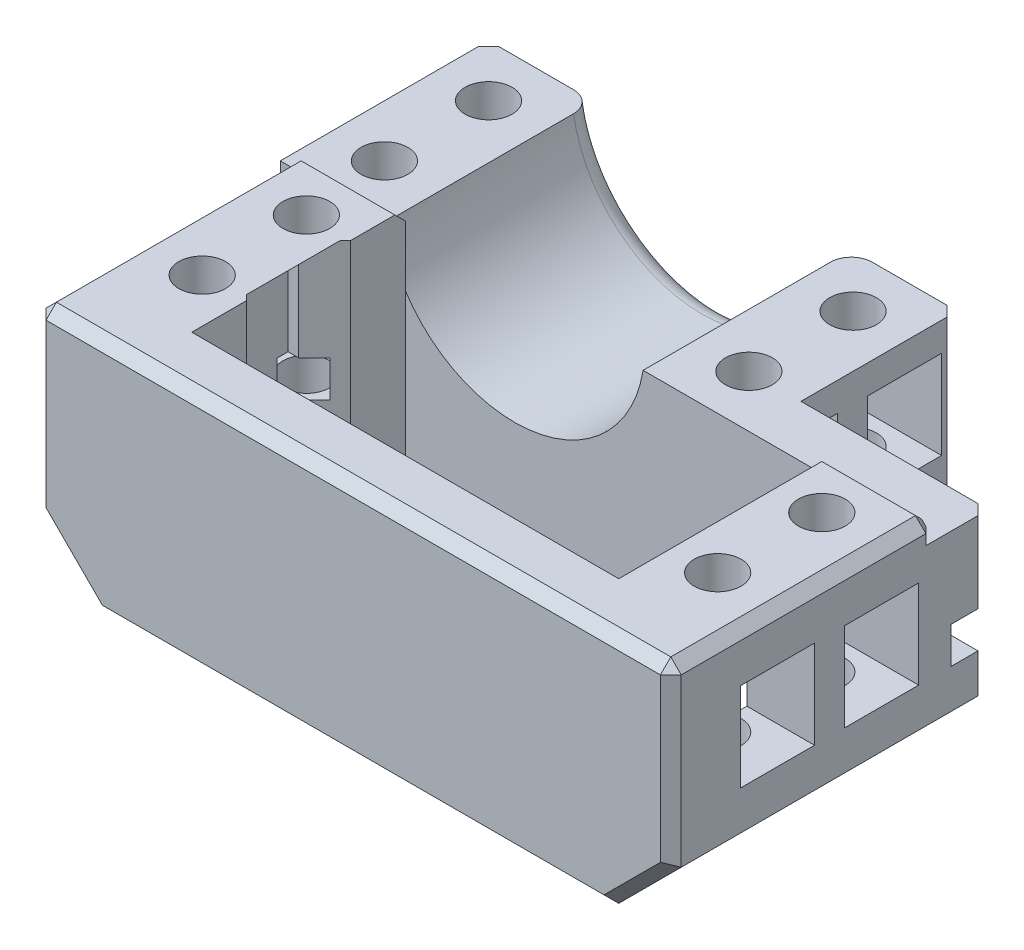
SolidWorks part; units mm, degrees
ref_plane "Front Plane" through (0, 0, 0) normal (0, 0, 1) x (1, 0, 0)
ref_plane "Top Plane" through (0, 0, 0) normal (0, 1, 0) x (1, 0, 0)
ref_plane "Right Plane" through (0, 0, 0) normal (1, 0, 0) x (0, 0, -1)
sketch "Sketch1" plane through (0, 0, 0) normal (0, 1, 0) x (1, 0, 0)
  line L0 (0, -10.25) -> (0, 10.25) construction
  line L1 (-20.5, 0) -> (20.5, 0) construction
  line L2 (-20.5, 10.25) -> (20.5, 10.25)
  line L3 (20.5, 10.25) -> (20.5, -10.25)
  line L4 (20.5, -10.25) -> (-20.5, -10.25)
  line L5 (-20.5, -10.25) -> (-20.5, 10.25)
  line L6 (0, -10.25) -> (0, -15.25) construction
  line L7 (0, -15.25) -> (-30.5, -15.25)
  line L8 (0, -15.25) -> (30.5, -15.25)
  line L9 (-30.5, -15.25) -> (-30.5, 30.25)
  line L10 (-30.5, 30.25) -> (30.5, 30.25)
  line L11 (30.5, 30.25) -> (30.5, -15.25)
  point P4 (0, 0)
  point P8 (0, 0)
  point P11 (0, 10.25)
  dimension "D1" = 41
  dimension "D2" = 20.5
  dimension "D3" = 5
  dimension "D4" = 30.5
  dimension "D5" = 30.5
  dimension "D6" = 45.5
extrude "Boss-Extrude1" add sketch "Sketch1" along normal blind 23
ref_plane "Plane1" through (0, 0, -30.25) normal (0, 0, -1) x (-1, 0, 0)
sketch "Sketch2" plane through (0, 0, -30.25) normal (0, 0, -1) x (-1, 0, 0)
  line L0 (0, 0) -> (0, 23) construction
  line L1 (-30.5, 23) -> (30.5, 23) construction
  line L2 (0, 23) -> (10, 23) construction
  circle A0 centre (10, 23) radius 12.5
  dimension "D2" = 25
  dimension "D1" = 10
extrude "Cut-Extrude1" cut sketch "Sketch2" against normal blind 20
ref_plane "Plane2" through (-30.5, 0, 0) normal (-1, 0, 0) x (0, 0, 1)
sketch "Sketch3" plane through (-30.5, 0, 0) normal (-1, 0, 0) x (0, 0, 1)
  line L0 (-30.25, 23) -> (-10.25, 23)
  line L1 (-30.25, 23) -> (15.25, 23) construction
  line L2 (-10.25, 23) -> (-10.25, 0)
  line L3 (-30.25, 0) -> (15.25, 0) construction
  line L4 (-10.25, 0) -> (-30.25, 0)
  line L5 (-30.25, 0) -> (-30.25, 23)
extrude "Boss-Extrude2" add sketch "Sketch3" along normal blind 2
ref_plane "Plane3" through (0, 23, 0) normal (0, 1, 0) x (1, 0, 0)
sketch "Sketch4" plane through (0, 23, 0) normal (0, 1, 0) x (1, 0, 0)
  line L0 (-22.5, 20.25) -> (-27.5, 20.25) construction
  line L1 (-22.5, 10.25) -> (-22.5, 30.25) construction
  line L2 (-27.5, 15.25) -> (-27.5, 25.25) construction
  line L3 (2.5, 20.25) -> (7.5, 20.25) construction
  line L4 (2.5, 30.25) -> (2.5, 10.25) construction
  line L5 (7.5, 15.25) -> (7.5, 25.25) construction
  circle A0 centre (-27.5, 25.25) radius 2.25
  circle A1 centre (-27.5, 15.25) radius 2.25
  circle A2 centre (7.5, 15.25) radius 2.25
  circle A3 centre (7.5, 25.25) radius 2.25
  point P7 (-27.5, 20.25)
  point P14 (7.5, 20.25)
  dimension "D4" = 4.5
  dimension "D5" = 4.5
  dimension "D6" = 4.5
  dimension "D7" = 4.5
  dimension "D1" = 10
  dimension "D2" = 5
  dimension "D3" = 5
extrude "Cut-Extrude2" cut sketch "Sketch4" against normal up to next
sketch "Sketch5" plane through (0, 23, 0) normal (0, 1, 0) x (1, 0, 0)
  line L0 (0, 0) -> (-24.75, 0) construction
  line L1 (-24.75, -5) -> (-24.75, 5) construction
  circle A0 centre (-24.75, 5) radius 2.25
  circle A1 centre (-24.75, -5) radius 2.25
  point P6 (-24.75, 0)
  dimension "D3" = 4.5
  dimension "D4" = 4.5
  dimension "D1" = 24.75
  dimension "D2" = 10
extrude "Cut-Extrude3" cut sketch "Sketch5" against normal up to next
mirror "Mirror1" about plane through (0, 0, 0) normal (1, 0, 0) of "Cut-Extrude3"
sketch "Sketch6" plane through (0, 0, -30.25) normal (0, 0, -1) x (-1, 0, 0)
  line L0 (-2.5, 23) -> (-12.5, 23) construction
  line L1 (-30.5, 23) -> (-2.5, 23) construction
  line L2 (-12.5, 23) -> (-12.5, 19)
  line L4 (-30.5, 23) -> (-30.5, 0) construction
  line L5 (-30.5, 19) -> (-30.5, 23)
  line L6 (-30.5, 23) -> (-12.5, 23)
  line L7 (-12.5, 19) -> (-12.5, 14) construction
  line L12 (-12.5, 9) -> (-12.5, 4) construction
  line L13 (-12.5, 4) -> (-12.5, 0)
  line L14 (-30.5, 0) -> (32.5, 0) construction
  line L15 (-12.5, 0) -> (-30.5, 0)
  line L16 (-30.5, 0) -> (-30.5, 4)
  line L18 (-30.5, 19) -> (-30.5, 4)
  line L19 (-12.5, 4) -> (-12.5, 19)
  dimension "D1" = 10
  dimension "D2" = 4
  dimension "D3" = 5
  dimension "D4" = 5
  dimension "D5" = 5
extrude "Cut-Extrude4" cut sketch "Sketch6" against normal blind 15
ref_plane "Plane4" through (12.5, 0, 0) normal (1, 0, 0) x (0, 0, -1)
sketch "Sketch7" plane through (12.5, 0, 0) normal (1, 0, 0) x (0, 0, -1)
  line L0 (30.25, 23) -> (30.25, 13.25) construction
  line L1 (30.25, 0) -> (30.25, 23) construction
  line L2 (30.25, 13.25) -> (30.25, 9.75) construction
  line L3 (30.25, 9.75) -> (30.25, 0) construction
  line L4 (30.25, 13.25) -> (28.75, 13.25) construction
  line L5 (28.75, 13.25) -> (21.65, 13.25)
  line L6 (21.65, 13.25) -> (18.75, 13.25) construction
  line L7 (18.75, 13.25) -> (11.65, 13.25)
  line L8 (28.75, 13.25) -> (28.75, 9.75)
  line L9 (28.75, 9.75) -> (21.65, 9.75)
  line L10 (21.65, 9.75) -> (21.65, 13.25)
  line L11 (18.75, 13.25) -> (18.75, 9.75)
  line L12 (18.75, 9.75) -> (11.65, 9.75)
  line L13 (11.65, 9.75) -> (11.65, 13.25)
  dimension "D1" = 9.75
  dimension "D2" = 3.5
  dimension "D3" = 1.5
  dimension "D4" = 7.1
  dimension "D5" = 2.9
  dimension "D6" = 7.1
extrude "Cut-Extrude5" cut sketch "Sketch7" against normal blind 9 and the other way through all
ref_plane "Plane5" through (-10, 0, 0) normal (1, 0, 0) x (0, 0, -1)
mirror "Mirror2" about plane through (-10, 0, 0) normal (1, 0, 0) of "Cut-Extrude5"
fillet "Fillet1" radius 2 1 edges at (-10, 10.5, -30.25)
sketch "Sketch8" plane through (-30.5, 0, 0) normal (-1, 0, 0) x (0, 0, 1)
  line L0 (0, 0) -> (0, 11.5) construction
  line L1 (-1.45, 11.5) -> (1.45, 11.5) construction
  line L3 (-1.45, 9.75) -> (-1.45, 13.25)
  line L4 (-1.45, 13.25) -> (-8.55, 13.25)
  line L5 (-8.55, 13.25) -> (-8.55, 9.75)
  line L6 (-8.55, 9.75) -> (-1.45, 9.75)
  line L7 (1.45, 9.75) -> (1.45, 13.25)
  line L8 (1.45, 13.25) -> (8.55, 13.25)
  line L9 (8.55, 13.25) -> (8.55, 9.75)
  line L10 (8.55, 9.75) -> (1.45, 9.75)
  point P6 (0, 11.5)
  point P9 (-1.45, 11.5)
  point P14 (1.45, 11.5)
  dimension "D1" = 11.5
  dimension "D2" = 2.9
  dimension "D3" = 3.5
  dimension "D4" = 7.1
  dimension "D5" = 7.1
extrude "Cut-Extrude6" cut sketch "Sketch8" against normal blind 9
mirror "Mirror3" about plane through (0, 0, 0) normal (1, 0, 0) of "Cut-Extrude6"
chamfer "Chamfer1" distance 5 angle 45 8 edges at (-30.5, 13.25, 5) (-30.5, 13.25, -5) (-32.5, 13.25, -15.2) (-32.5, 13.25, -25.2) (12.5, 13.25, -25.2) (12.5, 13.25, -17) (30.5, 13.25, -5) (30.5, 13.25, 5)
chamfer "Chamfer2" distance 8 1 edges at (-32.5, 0, -20.25)
chamfer "Chamfer3" distance 5 1 edges at (12.5, 0, -22.75)
chamfer "Chamfer4" distance 1 5 edges at (12.5, 14, -30.25) (10, 2.5, -30.25) (-8.5, 0, -30.25) (-28.5, 4, -30.25) (-32.5, 15.5, -30.25)
chamfer "Chamfer5" distance 6 1 edges at (30.5, 0, 0)
chamfer "Chamfer6" distance 1 13 edges at (21.5, 9.75, -15.25) (30.5, 7.875, -15.25) (-30.5, 14.5, 15.25) (-27.5, 3, 15.25) (0, 0, 15.25) (27.5, 3, 15.25) (30.5, 14.5, 15.25) (20.125, 13.25, -15.25) (30.5, 18.125, -15.25) (-30.5, 23, 2.5) (0, 23, 15.25) (30.5, 23, 0) (21.5, 23, -15.25)
chamfer "Chamfer7" distance 1 angle 45 2 edges at (17.125, 0, -15.25) (27, 2.5, -15.25)
ref_plane "Plane6" through (0, 33, 0) normal (0, 1, 0) x (1, 0, 0)
sketch "Sketch9" plane through (0, 33, 0) normal (0, 1, 0) x (1, 0, 0)
  line L0 (-32.5, 10.25) -> (30.5, 10.25)
  line L1 (30.5, 14.25) -> (30.5, -14.25) construction
  line L2 (30.5, 10.25) -> (30.5, 30.25)
  line L3 (30.5, 30.25) -> (-32.5, 30.25)
  line L4 (-32.5, 30.25) -> (-32.5, 10.25)
extrude "Cut-Extrude7" cut sketch "Sketch9" against normal blind 2 from surface starting at face at (24.75, 23, -2.75)
chamfer "Chamfer8" distance 1 6 edges at (30.5, 21.5, -10.25) (30, 22.5, -10.25) (25, 23, -10.25) (-30.5, 21.5, -10.25) (-30, 22.5, -10.25) (-25, 23, -10.25)
sketch "Sketch10" plane through (0, 33, 0) normal (0, 1, 0) x (1, 0, 0)
  line L0 (20.5, -2.5) -> (20.5, 2.5)
  line L1 (20.5, -10.25) -> (20.5, 9.25) construction
  line L2 (20.5, 2.5) -> (24, 2.5)
  line L3 (24, 2.5) -> (24, -2.5)
  line L4 (24, -2.5) -> (20.5, -2.5)
  line L5 (20.5, 0) -> (20.5, 10.25) construction
  point P5 (20.5, 0)
  dimension "D1" = 5
  dimension "D2" = 10.25
  dimension "D3" = 3.5
extrude "Cut-Extrude8" cut sketch "Sketch10" against normal up to next from offset 12 offset against normal yes
chamfer "Chamfer9" distance 2.5 2 edges at (20.5, 10.5, -2.5) (20.5, 10.5, 2.5)
mirror "Mirror4" about plane through (0, 0, 0) normal (1, 0, 0) of "Cut-Extrude8"
chamfer "Chamfer10" distance 2.5 3 edges at (-20.5, 10.5, 2.5) (-20.5, 21, 0) (-20.5, 10.5, -2.5)
